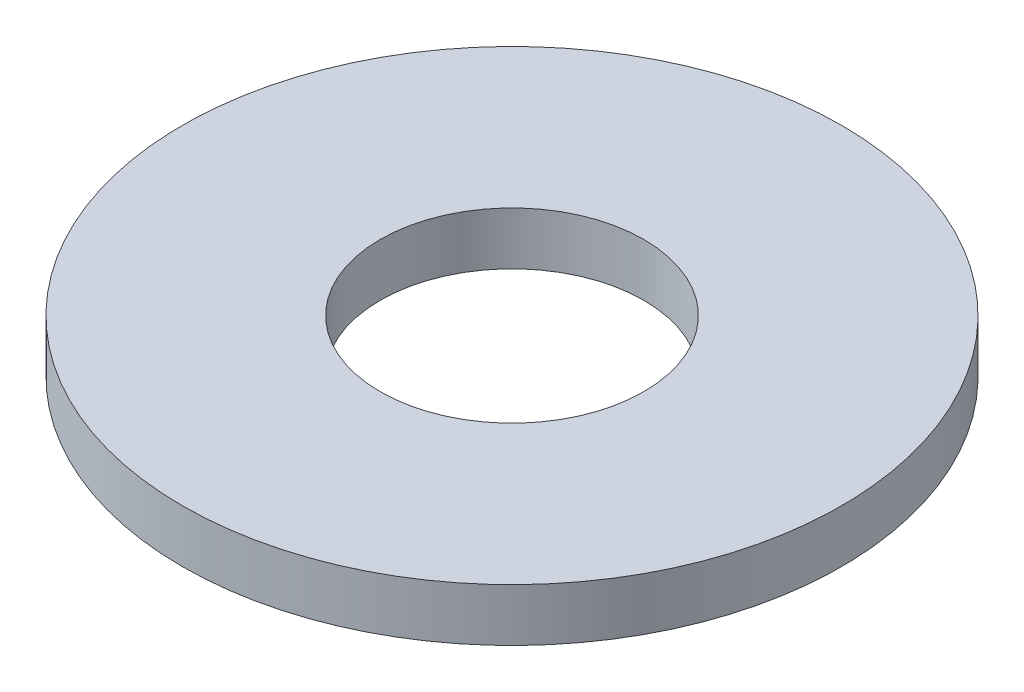
SolidWorks part; units mm, degrees
ref_plane "Front Plane" through (0, 0, 0) normal (0, 0, 1) x (1, 0, 0)
ref_plane "Top Plane" through (0, 0, 0) normal (0, 1, 0) x (1, 0, 0)
ref_plane "Right Plane" through (0, 0, 0) normal (1, 0, 0) x (0, 0, -1)
sketch "Sketch1" plane through (0, 0, 0) normal (0, 1, 0) x (1, 0, 0)
  circle A0 centre (0, 0) radius 37.5
  dimension "FLANGE_OD" = 75
extrude "Boss-Extrude1" add sketch "Sketch1" along normal blind 6
sketch "Sketch2" plane through (0, 0, 0) normal (0, 1, 0) x (1, 0, 0)
  circle A0 centre (0, 0) radius 15
  dimension "BORE_D" = 30
extrude "Cut-Extrude1" cut sketch "Sketch2" along normal through all
sketch "Sketch3" plane through (0, 6, 0) normal (0, 1, 0) x (1, 0, 0)
  circle A0 centre (0, 0) radius 10.2685 construction
  circle A1 centre (-10.2685, 0) radius 2.6517
  dimension "BOLT_D" = 5.3035
  dimension "BOLT_PCD" = 20.537
extrude "Cut-Extrude2" cut sketch "Sketch3" against normal blind 3.9765 rebuild error yes
pattern_circular "CirPattern1" count 8 over 360 rebuild error yes
